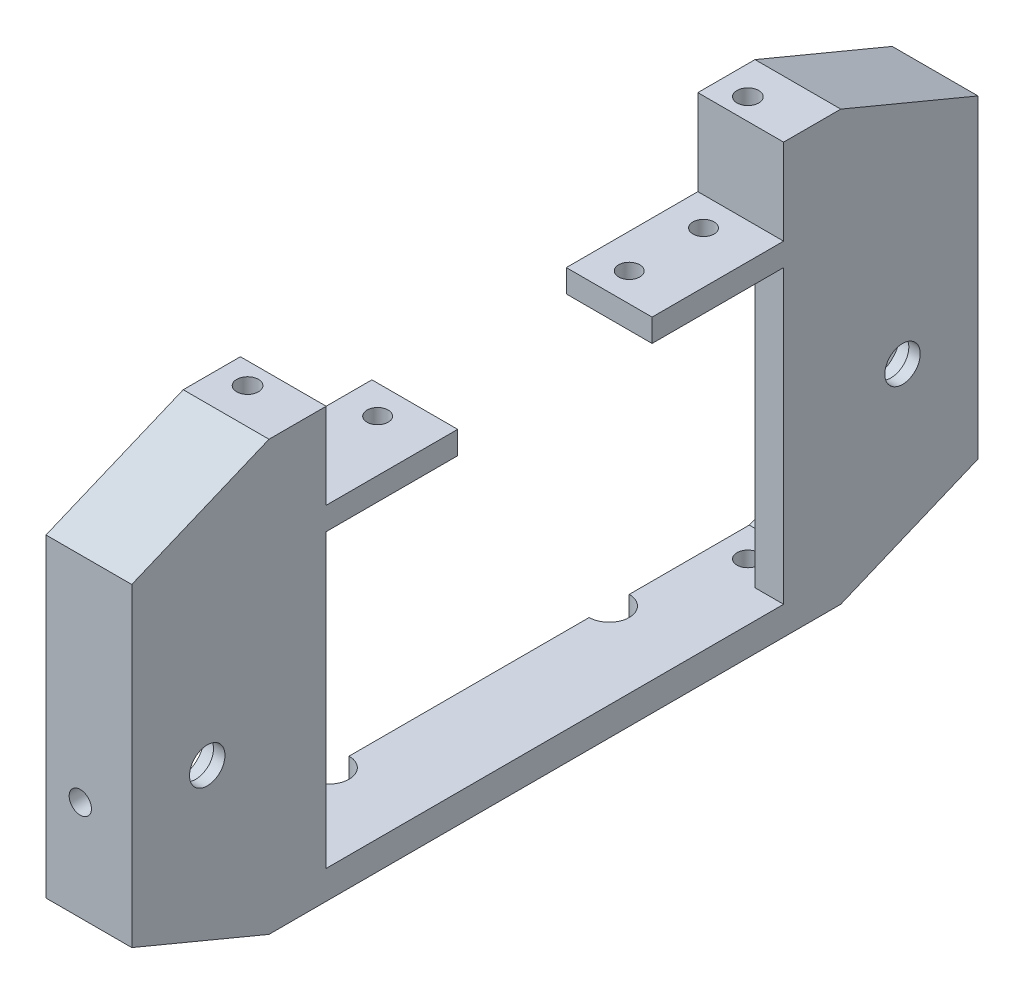
SolidWorks part; units mm, degrees
ref_plane "Front Plane" through (0, 0, 0) normal (0, 0, 1) x (1, 0, 0)
ref_plane "Top Plane" through (0, 0, 0) normal (0, 1, 0) x (1, 0, 0)
ref_plane "Right Plane" through (0, 0, 0) normal (1, 0, 0) x (0, 0, -1)
sketch "Sketch1" plane through (0, 0, 0) normal (0, 1, 0) x (1, 0, 0)
  line L1 (0, 0) -> (15, 0)
  line L2 (0, 0) -> (0, 34)
  line L3 (0, 34) -> (15, 34)
  line L4 (15, 0) -> (15, 34)
  dimension "D1" = 34
  dimension "D2" = 15
extrude "Boss-Extrude1" add sketch "Sketch1" along normal blind 75
sketch "Sketch2" plane through (15, 0, 0) normal (1, 0, 0) x (0, 0, -1)
  line L5 (34, 0) -> (24, 0)
  line L6 (0, 0) -> (34, 0) construction
  line L7 (24, 0) -> (0, 10)
  line L11 (0, 75) -> (0, 0) construction
  line L13 (0, 10) -> (0, 65)
  line L24 (0, 65) -> (24, 75)
  line L25 (0, 75) -> (34, 75) construction
  line L26 (24, 75) -> (34, 75)
  line L28 (34, 75) -> (34, 70)
  line L29 (34, 75) -> (34, 0) construction
  line L33 (34, 70) -> (25, 70)
  line L34 (25, 70) -> (5, 61.6667)
  line L35 (5, 61.6667) -> (5, 13.3333)
  line L36 (5, 13.3333) -> (25, 5)
  line L37 (25, 5) -> (34, 5)
  line L38 (34, 5) -> (34, 0)
  line L39 (0, 10) -> (0, 0)
  line L40 (0, 0) -> (24, 0)
  line L41 (0, 65) -> (0, 75)
  line L42 (0, 75) -> (24, 75)
  line M4 (0, 0) -> (34, 0)
  line M5 (34, 0) -> (34, 75)
  line M6 (34, 75) -> (0, 75)
  line M7 (0, 75) -> (0, 0)
  dimension "D1" = 5
  dimension "D2" = 5
  dimension "D3" = 10
  dimension "D4" = 10
  dimension "D5" = 24
  dimension "D6" = 24
  dimension "D7" = 5
  dimension "D8" = 5
  dimension "D9" = 5
extrude "Cut-Extrude5" cut sketch "Sketch2" against normal up to surface (15 mm away) contours L24 M7 M6 | L7 M4 M7 region at (15, 3.3333, -8) region at (15, 71.6667, -8) up to face at (0, 37.5, -17)
extrude "Cut-Extrude6" cut sketch "Sketch2<5>" along normal offset from surface (10 mm away) 5 from surface contours L36 L37 L33 L34 L35 M5 region at (15, 37.5, -20.2598) up to face at (15, 37.5, -19.3333) starting at face at (0, 37.5, -19.3333)
sketch "Sketch2<5>" plane through (15, 0, 0) normal (1, 0, 0) x (0, 0, -1) same geometry as "Sketch2"
sketch "Sketch13" plane through (15, 0, 0) normal (1, 0, 0) x (0, 0, -1)
  line L0 (34, 75) -> (34, 0) construction
  line L1 (34, 60) -> (57, 60)
  line L2 (34, 60) -> (34, 56)
  line L3 (34, 56) -> (57, 56)
  line L4 (57, 60) -> (57, 56)
  line L5 (24, 75) -> (34, 75) construction
  line L9 (41.5281, 56) -> (35.8712, 56)
  line M11 (34, 0) -> (34, 75)
  dimension "D1" = 15
  dimension "D2" = 23
  dimension "D3" = 4
extrude "Boss-Extrude4" add sketch "Sketch13" against normal blind 15 contours L3 M11 | L4 L1 L3 M11 region at (15, 58, -45.5)
sketch "Sketch14" plane through (0, 60, 0) normal (0, 1, 0) x (1, 0, 0)
  line L0 (15, 34) -> (0, 34) construction
  line L1 (6, 52) -> (6, 39) construction
  line L2 (0, 34) -> (0, 57) construction
  circle A0 centre (6, 39) radius 1.85
  circle A1 centre (6, 52) radius 1.85
  dimension "D3" = 3.7
  dimension "D1" = 5
  dimension "D2" = 13
  dimension "D4" = 6
extrude "Cut-Extrude8" cut sketch "Sketch14" against normal through all
sketch "Sketch15" plane through (10, 0, 0) normal (-1, 0, 0) x (0, 0, 1)
  line L0 (-34, 56) -> (-57, 56) construction
  line L1 (-34, 70) -> (-25, 70)
  line L2 (-34, 70) -> (-34, 56)
  line L3 (-34, 56) -> (-25, 56)
  line L4 (-25, 70) -> (-25, 56)
extrude "Boss-Extrude5" add sketch "Sketch15" along normal up to surface (10 mm away) up to face at (0, 37.5, -20.3333)
sketch "Sketch5" plane through (0, 75, 0) normal (0, 1, 0) x (1, 0, 0)
  line L0 (15, 24) -> (15, 34) construction
  line L8 (15, 34) -> (0, 34) construction
  circle A0 centre (5, 30.25) radius 1.9
  dimension "D3" = 3.8
  dimension "D1" = 10
  dimension "D2" = 3.75
extrude "Cut-Extrude4" cut sketch "Sketch5" against normal up to surface (75 mm away) up to face at (7.5, 0, -29)
sketch "Sketch11" plane through (15, 0, 0) normal (1, 0, 0) x (0, 0, -1)
  line L0 (34, 75) -> (34, 60) construction
  line L1 (24, 0) -> (34, 0) construction
  circle A0 centre (13.2, 31) radius 4.6
  dimension "D1" = 9.2
  dimension "D2" = 20.8
  dimension "D3" = 31
extrude "Cut-Extrude7" cut sketch "Sketch11" against normal blind 10
sketch "Sketch12" plane through (15, 0, 0) normal (1, 0, 0) x (0, 0, -1)
  line L6 (34, 75) -> (24, 75)
  line L7 (24, 75) -> (0, 65)
  line L8 (0, 65) -> (0, 10)
  line L9 (0, 10) -> (24, 0)
  line L10 (24, 0) -> (34, 0)
  line L11 (34, 0) -> (34, 56)
  line L12 (34, 75) -> (24, 75)
  line L13 (24, 75) -> (0, 65)
  line L14 (0, 65) -> (0, 10)
  line L15 (0, 10) -> (24, 0)
  line L16 (24, 0) -> (34, 0)
  line L17 (34, 0) -> (34, 56)
  line L22 (34, 56) -> (57, 56)
  line L23 (34, 56) -> (57, 56)
  line L24 (57, 56) -> (57, 60)
  line L25 (57, 56) -> (57, 60)
  line L26 (57, 60) -> (34, 60)
  line L27 (57, 60) -> (34, 60)
  line L28 (34, 60) -> (34, 75)
  line L29 (34, 60) -> (34, 75)
  circle A0 centre (13.2, 31) radius 4.6 construction
  circle A1 centre (13.2, 31) radius 4.6
  circle A2 centre (13.2, 31) radius 3.1
  circle M7 centre (13.2, 31) radius 4.6
  dimension "D2" = 1.5
  dimension "D1" = 0
extrude "Boss-Extrude3" add sketch "Sketch12" against normal blind 2 contours A2 M7 region at (15, 31, -8.7301)
sketch "Sketch16" plane through (0, 56, 0) normal (0, -1, 0) x (1, 0, 0)
  circle A0 centre (5, -30.25) radius 3.1
  dimension "D1" = 6.2
extrude "Cut-Extrude9" [suppressed] cut sketch "Sketch16" against normal blind 5
sketch "Sketch17" plane through (0, 5, 0) normal (0, 1, 0) x (1, 0, 0)
  circle A0 centre (5, 30.25) radius 3
  dimension "D1" = 6
extrude "Cut-Extrude10" [suppressed] cut sketch "Sketch17" against normal blind 1
sketch "Sketch18" plane through (15, 0, 0) normal (1, 0, 0) x (0, 0, -1)
  line L0 (34, 56) -> (34, 0) construction
  line L1 (57, 60) -> (57, 56) construction
  circle A0 centre (34, 75) radius 6
  circle A1 centre (0, 65) radius 6
  circle A3 centre (57, 58) radius 6
  circle A4 centre (34, 53.3172) radius 6
  circle A5 centre (34, 0) radius 6
  circle A6 centre (0, 10) radius 6
  dimension "D1" = 12
extrude "Boss-Extrude6" [suppressed] add sketch "Sketch18" against normal blind 0.1
sketch "Sketch20" plane through (0, 0, 0) normal (-1, 0, 0) x (0, 0, 1)
  line L1 (-34, 0) -> (-74, 0)
  line L2 (-34, 0) -> (-34, 5)
  line L3 (-34, 5) -> (-74, 5)
  line L4 (-74, 0) -> (-74, 5)
  line L7 (-25, 5) -> (-34, 5) construction
  dimension "D1" = 40
extrude "Boss-Extrude8" add sketch "Sketch20" against normal up to surface (15 mm away) up to face at (15, 45.7, -29.8)
sketch "Sketch21" plane through (0, 5, 0) normal (0, 1, 0) x (1, 0, 0)
  line L0 (0, 34) -> (0, 57) construction
  line L1 (15, 74) -> (0, 74) construction
  circle A0 centre (0, 49.5) radius 3.5
  dimension "D1" = 7
  dimension "D2" = 24.5
extrude "Cut-Extrude11" cut sketch "Sketch21" against normal through all
mirror "Mirror3" about plane through (55.3113, 0, -74) normal (0, 0, -1) of bodies 126
sketch "Sketch22" plane through (0, 0, 0) normal (0, 0, 1) x (1, 0, 0)
  line L0 (0, 0) -> (15, 0) construction
  line L1 (15, 65) -> (15, 10) construction
  circle A0 centre (6, 27.5) radius 1.95
  dimension "D1" = 3.9
  dimension "D2" = 27.5
  dimension "D3" = 9
extrude "Cut-Extrude12" cut sketch "Sketch22" against normal through all
